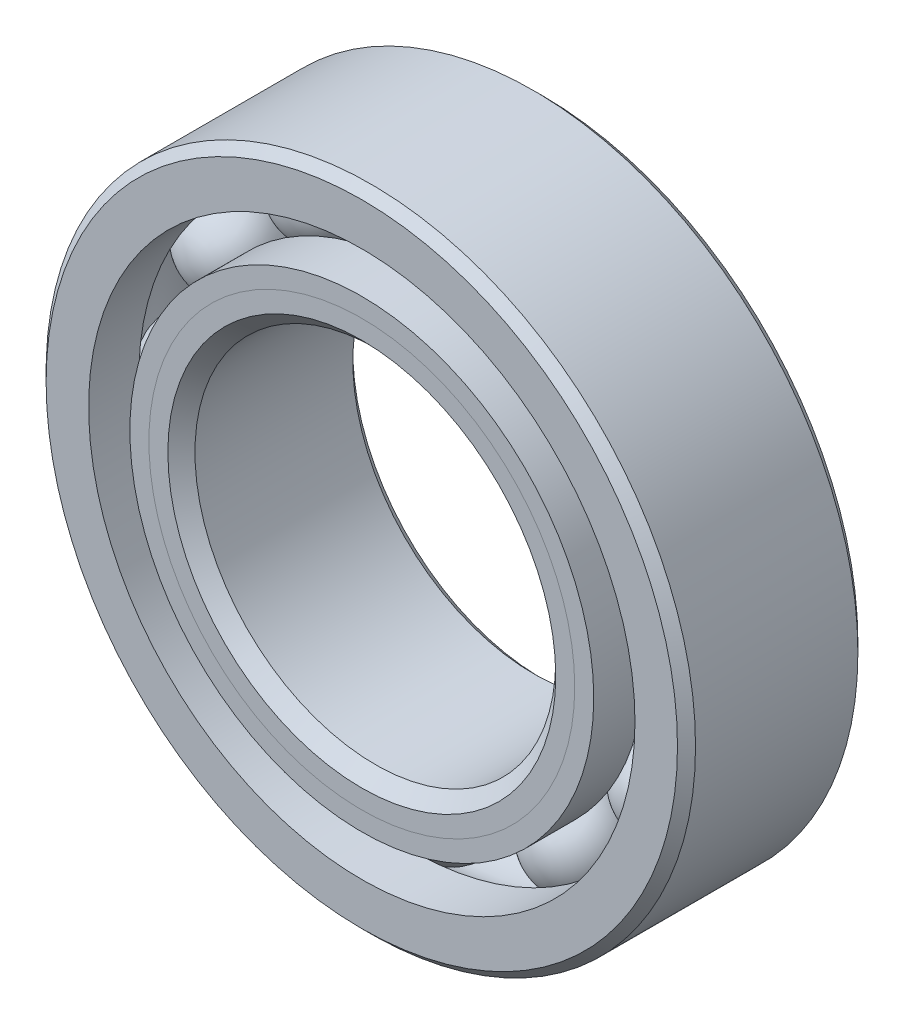
SolidWorks part; units mm, degrees
ref_plane "Front Plane" through (0, 0, 0) normal (0, 0, 1) x (1, 0, 0)
ref_plane "Top Plane" through (0, 0, 0) normal (0, 1, 0) x (1, 0, 0)
ref_plane "Right Plane" through (0, 0, 0) normal (1, 0, 0) x (0, 0, -1)
sketch "Sketch1" plane through (0, 0, 0) normal (1, 0, 0) x (0, 0, -1)
  line L0 (-3.9688, 0) -> (3.9688, 0) construction
  line L1 (0, 14.2875) -> (0, -14.2875) construction
  line L2 (3.5719, 14.2875) -> (-3.5719, 14.2875)
  line L3 (-3.5719, 14.2875) -> (-3.9688, 13.8906)
  line L4 (-3.9688, 13.8906) -> (-3.9688, 12.0196)
  line L5 (-3.9688, 12.0196) -> (-1.7639, 12.0196)
  line L6 (3.9688, 12.0196) -> (1.7639, 12.0196)
  line L7 (3.9688, 13.8906) -> (3.9688, 12.0196)
  line L8 (3.5719, 14.2875) -> (3.9688, 13.8906)
  line L9 (0, 14.2875) -> (0, 11.1125) construction
  line L10 (0, 11.1125) -> (0, 7.9375) construction
  arc A0 (-1.7639, 12.0196) -> (1.7639, 12.0196) centre (0, 11.1125) cw
  point P14 (0, 7.9375)
  dimension "Width" = 7.9375
  dimension "OD" = 28.575
  dimension "D1" = 45
  dimension "D2" = 0.3969
  dimension "D3" = 3.5278
  dimension "D4" = 0.9071
revolve "Revolve1" add sketch "Sketch1" angle 360 about L0
sketch "Sketch2" plane through (0, 0, 0) normal (1, 0, 0) x (0, 0, -1)
  line L0 (-3.9688, 10.2054) -> (-1.7639, 10.2054)
  line L1 (-3.9688, 13.8906) -> (-3.9688, -13.8906) construction
  line L2 (-3.9688, 10.2054) -> (-3.9688, 9.3693)
  line L3 (-3.9688, 9.3693) -> (-3.1327, 8.5333)
  line L4 (-3.1327, 8.5333) -> (0, 8.5333)
  line L5 (0, 14.2875) -> (0, -14.2875) construction
  line L6 (0, 8.5333) -> (0, 9.129)
  line L7 (0, 9.129) -> (0, 7.9375) construction
  line L8 (-3.9688, 10.2054) -> (-3.9688, 8.5333) construction
  line L9 (-3.9688, 8.5333) -> (-3.1327, 8.5333) construction
  arc A0 (-1.7639, 10.2054) -> (0, 9.129) centre (0, 11.1125) ccw
  arc A1 (1.7639, 12.0196) -> (-1.7639, 12.0196) centre (0, 11.1125) ccw construction
  circle A2 centre (0, 11.1125) radius 1.9835 construction
  dimension "D1" = 45
revolve "Revolve2" add sketch "Sketch2" angle 360 about L0
sketch "Sketch3" plane through (0, 0, 0) normal (1, 0, 0) x (0, 0, -1)
  line L0 (-3.9688, 9.3693) -> (-3.1327, 8.5333)
  line L1 (-3.1327, 8.5333) -> (0, 8.5333)
  line L2 (0, 8.5333) -> (0, 9.129)
  line L3 (-3.9688, 9.3693) -> (-3.9688, 8.5333)
  line L4 (-3.9688, 10.2054) -> (-3.9688, 8.5333) construction
  line L5 (-3.9688, 8.5333) -> (-3.373, 7.9375)
  line L6 (-3.373, 7.9375) -> (3.5719, 7.9375)
  line L7 (3.5719, 14.2875) -> (3.5719, -14.2875) construction
  line L8 (3.5719, 7.9375) -> (3.9688, 8.3344)
  line L9 (3.9688, -13.8906) -> (3.9688, 13.8906) construction
  line L10 (3.9688, 8.3344) -> (3.9688, 10.2054)
  line L11 (3.9688, 10.2054) -> (1.7639, 10.2054)
  line L13 (3.5719, 14.2875) -> (3.9688, 13.8906) construction
  circle A0 centre (0, 11.1125) radius 1.9835 construction
  arc A1 (1.7639, 10.2054) -> (0, 9.129) centre (0, 11.1125) cw
revolve "Revolve3" add sketch "Sketch3" angle 360 about L0
sketch "Sketch4" plane through (0, 0, 0) normal (1, 0, 0) x (0, 0, -1)
  line L0 (-1.9835, 11.1125) -> (1.9835, 11.1125)
  circle A1 centre (0, 11.1125) radius 1.9835 construction
  arc A2 (-1.9835, 11.1125) -> (1.9835, 11.1125) centre (0, 11.1125) cw
  arc A3 (1.7639, 12.0196) -> (-1.7639, 12.0196) centre (0, 11.1125) ccw construction
revolve "Revolve4" add sketch "Sketch4" angle 360 about L0
ref_axis "Axis1" through (0, 0, -3.9688) along (0, 0, 1)
pattern_circular "CirPattern1" count 12 every 30 about axis through (0, 0, -3.9688) along (0, 0, 1) of bodies 104
equation "\"D2@Sketch1\" = \"Width@Sketch1\"*.05"
equation "\"D3@Sketch1\" = \"Width@Sketch1\"/2.25"
equation "\"D4@Sketch1\" = (((\"OD@Sketch1\"-\"Width@Sketch1\")/2)/3.25)/3.5"
equation "\"D2@CirPattern1\" = 360/\"Balls@CirPattern1\""
